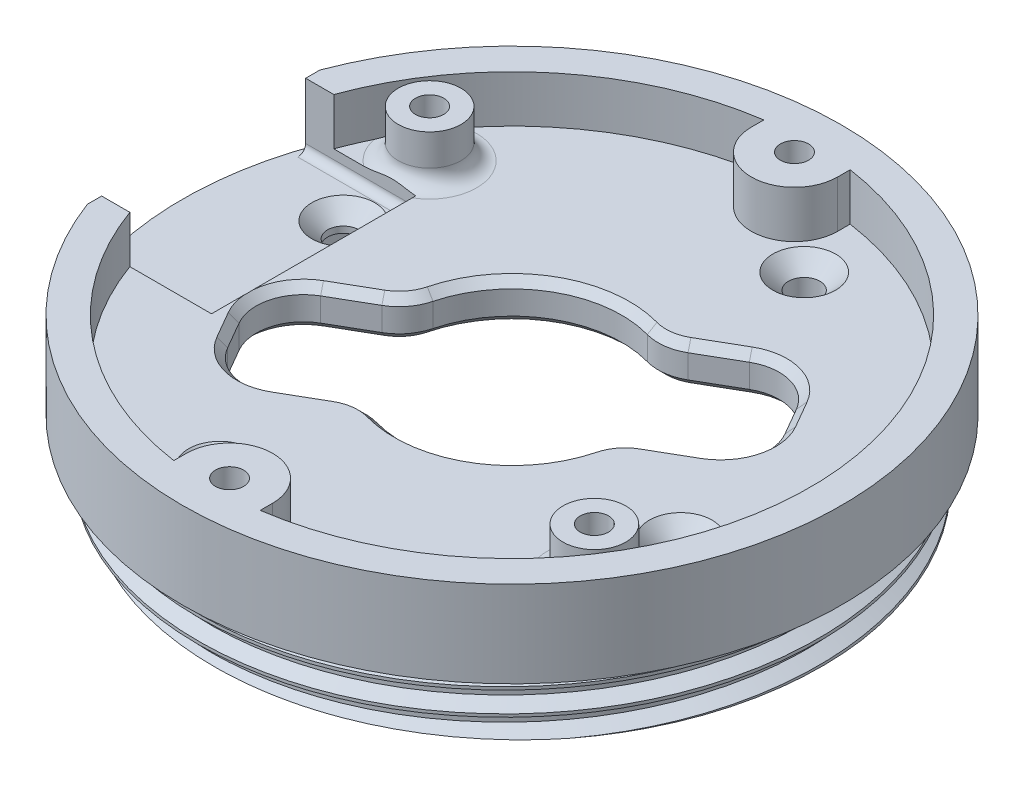
SolidWorks part; units mm, degrees
ref_plane "Front plane" through (0, 0, 0) normal (0, 0, 1) x (1, 0, 0)
ref_plane "Top plane" through (0, 0, 0) normal (0, 1, 0) x (1, 0, 0)
ref_plane "Right plane" through (0, 0, 0) normal (1, 0, 0) x (0, 0, -1)
ref_axis "Axis X" through (0, 0, 0) along (1, 0, 0)
ref_axis "Axis Y" through (0, 0, 0) along (0, 1, 0)
ref_axis "Axis Z" through (0, 0, 0) along (0, 0, 1)
sketch "Sketch1" plane through (0, 0, 0) normal (0, 1, 0) x (1, 0, 0)
  line L0 (0, 0) -> (0, 21) construction
  circle A0 centre (0, 0) radius 21
  circle A8 centre (0, 0) radius 7
  circle A9 centre (0, 0) radius 18 construction
  circle A10 centre (0, 18) radius 0.9
  circle A11 centre (0, -18) radius 0.9
  circle A12 centre (0, 0) radius 15.3 construction
  dimension "D1" = 42
  dimension "D9" = 14
  dimension "D10" = 36
  dimension "D11" = 1.8
  dimension "D12" = 1.8
  dimension "D5" = 30.6
extrude "Extrude1" add sketch "Sketch1" along normal blind 2.5
sketch "Sketch3" plane through (0, 2.5, 0) normal (0, 1, 0) x (1, 0, 0)
  line L0 (-2.75, 18) -> (-2.75, 18.7999)
  line L1 (2.75, 18) -> (2.75, 18.7999)
  line L2 (2.75, -18) -> (2.75, -18.7999)
  line L3 (-2.75, -18) -> (-2.75, -18.7999)
  line L5 (14.15, 8.9) -> (-14.15, 8.9) construction
  line L6 (14.15, 8.9) -> (14.15, -8.9) construction
  line L7 (14.15, -8.9) -> (-14.15, -8.9) construction
  line L8 (-14.15, 8.9) -> (-14.15, -8.9) construction
  line L9 (14.15, 8.9) -> (-14.15, -8.9) construction
  line L10 (14.15, -8.9) -> (-14.15, 8.9) construction
  arc A0 (-2.75, 18.7999) -> (-2.75, -18.7999) centre (0, 0) ccw
  circle A1 centre (0, 18) radius 0.9
  circle A2 centre (0, 0) radius 21 construction
  arc A3 (-2.75, 18) -> (2.75, 18) centre (0, 18) ccw
  arc A4 (2.75, -18) -> (-2.75, -18) centre (0, -18) ccw
  circle A5 centre (0, 0) radius 21
  arc A6 (-2.6256, -18.8177) -> (2.6256, -18.8177) centre (0, -18) ccw construction
  arc A7 (2.6256, 18.8177) -> (-2.6256, 18.8177) centre (0, 18) ccw construction
  arc A8 (2.6256, 18.8177) -> (-2.6256, 18.8177) centre (0, 0) ccw construction
  arc A9 (2.75, -18.7999) -> (2.75, 18.7999) centre (0, 0) ccw
  arc A10 (-2.6256, -18.8177) -> (2.6256, -18.8177) centre (0, 0) ccw construction
  circle A11 centre (0, -18) radius 0.9
  arc A12 (2.75, 18.7999) -> (2.6256, 18.8177) centre (0, 0) ccw construction
  arc A13 (2.75, 18) -> (2.6256, 18.8177) centre (0, 18) ccw construction
  arc A14 (-2.6256, 18.8177) -> (-2.75, 18.7999) centre (0, 0) ccw construction
  arc A15 (-2.6256, 18.8177) -> (-2.75, 18) centre (0, 18) ccw construction
  arc A16 (-2.75, -18) -> (-2.6256, -18.8177) centre (0, -18) ccw construction
  arc A17 (-2.75, -18.7999) -> (-2.6256, -18.8177) centre (0, 0) ccw construction
  arc A18 (2.6256, -18.8177) -> (2.75, -18) centre (0, -18) ccw construction
  arc A19 (2.6256, -18.8177) -> (2.75, -18.7999) centre (0, 0) ccw construction
  circle A20 centre (-14.15, 8.9) radius 2 construction
  circle A21 centre (14.15, -8.9) radius 2.2569 construction
  dimension "D2" = 5.5
  dimension "D3" = 5.5
  dimension "D5" = 1.8
  dimension "D6" = 1.8
  dimension "D9" = 4
  dimension "D10" = 4.5137
  dimension "D7" = 28.3
  dimension "D8" = 17.8
extrude "Extrude2" add sketch "Sketch3" along normal blind 3
sketch "Sketch7" plane through (0, 5.5, 0) normal (0, 1, 0) x (1, 0, 0)
  line L0 (0, 0) -> (-21, 0) construction
  line L1 (-17.4571, 7.5) -> (-17.4571, -7.5) construction
  line L2 (-15, 11.6619) -> (-15, -11.6619)
  circle A0 centre (0, 0) radius 21 construction
  arc A1 (-2.75, 18.7999) -> (-2.75, -18.7999) centre (0, 0) ccw construction
  arc A2 (-2.75, 18.7999) -> (-2.75, -18.7999) centre (0, 0) ccw construction
  arc A4 (-15, 11.6619) -> (-15, -11.6619) centre (0, 0) ccw
  arc A5 (-15, -11.6619) -> (-15, 11.6619) centre (0, 0) ccw construction
  dimension "D1" = 15
  dimension "D4" = 15
extrude "Extrude8" [suppressed] add sketch "Sketch7" against normal through all
sketch "Sketch4" plane through (0, 5.5, 0) normal (0, 1, 0) x (1, 0, 0)
  line L0 (0, 0) -> (-21, 0) construction
  line L1 (-21, 7.5) -> (-21, -7.5)
  line L3 (-12.65, 6.5) -> (-12.65, -6.5)
  line L6 (-21, 7.5) -> (-19.65, 7.5)
  line L8 (-19.65, 6.5) -> (-12.65, 6.5)
  line L9 (-19.65, -6.5) -> (-12.65, -6.5)
  line L10 (-21, -7.5) -> (-19.65, -7.5)
  line L11 (-19.65, 6.5) -> (-19.65, -6.5) construction
  line L12 (-19.65, 7.5) -> (-19.65, 6.5)
  line L13 (-19.65, -6.5) -> (-19.65, -7.5)
  circle A0 centre (0, 0) radius 21 construction
  point P11 (-21, 0)
  point P15 (-19.65, -7.5)
  point P19 (-12.65, 0)
  point P21 (-19.65, 7.5)
  dimension "D2" = 15
  dimension "D3" = 13
  dimension "D5" = 19.65
  dimension "D1" = 7
extrude "Extrude3" cut sketch "Sketch4" against normal blind 4.1
sketch "Sketch9" plane through (0, 0, 0) normal (0, -1, 0) x (1, 0, 0)
  circle A0 centre (0, 18) radius 1
  circle A1 centre (0, -18) radius 1
  dimension "D1" = 2
  dimension "D2" = 2
extrude "Extrude5" add sketch "Sketch9" against normal blind 1
sketch "Sketch8" plane through (0, 0, 0) normal (0, -1, 0) x (1, 0, 0)
  circle A0 centre (0, 0) radius 18
  circle A1 centre (0, 0) radius 18.95
  dimension "D1" = 36
  dimension "D2" = 0.95
extrude "Extrude6" add sketch "Sketch8" along normal blind 4
thread "Thread1" pitch 1.5 method extrude trim with start face yes trim with end face yes profile "Sketch11" start angle 0, offset 2, length 0, pitch 1.5, diameter 37.9
ref_plane "Plane1" through (18.95, -6, 0) normal (0, 0, 1) x (1, 0, 0)
sketch "Sketch11" plane through (18.95, -6, 0) normal (0, 0, 1) x (1, 0, 0)
  line L0 (0, 0) -> (0, 1.5) construction
  line L1 (0, 0) -> (0.8119, 0.4687)
  line L2 (0.8119, 0.4687) -> (0.8119, 0.6562)
  line L3 (0.8119, 0.6562) -> (0, 1.125)
  line L4 (0.8119, 0.5625) -> (0, 0.5625) construction
  line L11 (0, 0) -> (0, 1.125)
  point P2 (0, 0)
  dimension "Pitch" = 1.5
  dimension "Profile_Angle" = 60
  dimension "Profile_Land" = 0.1875
  dimension "Profile_Height" = 0.8119
fillet "Fillet3" [suppressed] radius 0.5
sketch "Sketch28" plane through (0, 1.4, 0) normal (0, 1, 0) x (1, 0, 0)
  line L0 (-17.8536, 6.5) -> (-17.8536, -6.5)
  arc A0 (-17.8536, 6.5) -> (-17.8536, -6.5) centre (0, 0) ccw
  arc A1 (-17.8536, -6.5) -> (-17.8536, 6.5) centre (0, 0) ccw construction
extrude "Extrude15" [suppressed] add sketch "Sketch28" against normal up to surface (0.6 mm away)
fillet "Fillet4" radius 0.5 2 edges at (-16.15, 1.4, 6.5) (-16.15, 1.4, -6.5)
sketch "Sketch22" plane through (0, 2.5, 0) normal (0, 1, 0) x (1, 0, 0)
  line L1 (14.15, 8.9) -> (-14.15, 8.9) construction
  line L2 (14.15, 8.9) -> (14.15, -8.9) construction
  line L3 (14.15, -8.9) -> (-14.15, -8.9) construction
  line L4 (-14.15, 8.9) -> (-14.15, -8.9) construction
  line L5 (14.15, 8.9) -> (-14.15, -8.9) construction
  line L6 (14.15, -8.9) -> (-14.15, 8.9) construction
  circle A1 centre (-14.15, 8.9) radius 2
  circle A2 centre (14.15, -8.9) radius 2
  point P0 (0, 0)
  dimension "D3" = 4
  dimension "D4" = 4
  dimension "D1" = 28.3
  dimension "D2" = 17.8
extrude "Extrude9" add sketch "Sketch22" along normal blind 3
sketch "Sketch23" plane through (0, 5.5, 0) normal (0, 1, 0) x (1, 0, 0)
  line L0 (0, 0) -> (3.9348, 14.6848) construction
  line L1 (0, 0) -> (0, 15.2028) construction
  line L6 (0, 0) -> (9.4981, -8.8746) construction
  circle A0 centre (14.15, -8.9) radius 0.9
  circle A1 centre (-14.15, 8.9) radius 0.9
  circle A2 centre (0, 0) radius 15.2028 construction
  circle A4 centre (3.9348, 14.6848) radius 1
  circle A5 centre (14.6848, -3.9348) radius 1
  circle A6 centre (-3.9348, -14.6848) radius 1
  circle A7 centre (-14.6848, 3.9348) radius 1
  point P21 (0, 0)
  dimension "D1" = 1.8
  dimension "D2" = 1.8
  dimension "D4" = 30.4056
  dimension "D5" = 2
  dimension "D3" = 15
extrude "Extrude10" cut sketch "Sketch23" against normal through all
sketch "Sketch24" plane through (0, 2.5, 0) normal (0, 1, 0) x (1, 0, 0)
  line L0 (3.9348, 14.6848) -> (0, 0) construction
  line L1 (8.6603, 5) -> (-8.6603, -5) construction
  line L2 (7.6603, 6.7321) -> (9.6603, 3.2679) construction
  line L3 (10.2583, 8.2321) -> (12.2583, 4.7679)
  line L4 (5.0622, 5.2321) -> (7.0622, 1.7679)
  line L5 (0, 0) -> (3.9532, -6.8471) construction
  line L6 (-9.6603, -3.2679) -> (-7.6603, -6.7321) construction
  line L7 (-12.2583, -4.7679) -> (-10.2583, -8.2321)
  line L8 (-7.0622, -1.7679) -> (-5.0622, -5.2321)
  arc A0 (10.2583, 8.2321) -> (5.0622, 5.2321) centre (7.6603, 6.7321) ccw
  arc A1 (7.0622, 1.7679) -> (12.2583, 4.7679) centre (9.6603, 3.2679) ccw
  arc A2 (-12.2583, -4.7679) -> (-7.0622, -1.7679) centre (-9.6603, -3.2679) cw
  arc A3 (-5.0622, -5.2321) -> (-10.2583, -8.2321) centre (-7.6603, -6.7321) cw
  circle A4 centre (3.9348, 14.6848) radius 1 construction
  point P6 (0, 0)
  point P9 (8.6603, 5)
  point P17 (-8.6603, -5)
  dimension "D3" = 4
  dimension "D1" = 10
  dimension "D2" = 6
  dimension "D4" = 45
extrude "Extrude11" [suppressed] cut sketch "Sketch24" against normal blind 40
chamfer "Chamfer1" [suppressed] distance 0.5 angle 45
sketch "Sketch25" plane through (0, 2.5, 0) normal (0, 1, 0) x (1, 0, 0)
  line L0 (9.2583, 9.9641) -> (-13.2583, -3.0359)
  line L1 (9.2583, 9.9641) -> (13.2583, 3.0359)
  line L2 (-13.2583, -3.0359) -> (-9.2583, -9.9641)
  line L3 (13.2583, 3.0359) -> (-9.2583, -9.9641)
  line L4 (9.2583, 9.9641) -> (-9.2583, -9.9641) construction
  line L5 (-13.2583, -3.0359) -> (13.2583, 3.0359) construction
  line L6 (0, 0) -> (3.9348, 14.6848) construction
  circle A0 centre (3.9348, 14.6848) radius 1 construction
  point P1 (0, 0)
  dimension "D1" = 26
  dimension "D2" = 45
  dimension "D3" = 8
extrude "Extrude12" cut sketch "Sketch25" against normal through all
fillet "Fillet5" radius 3 8 edges at (6.9749, 1.25, 0.5918) (2.9749, 1.25, -6.3364) (-6.9749, 1.25, -0.5918) (-2.9749, 1.25, 6.3364) (-9.2583, 1.25, 9.9641) (-13.2583, 0.7, 3.0359) (13.2583, 1.25, -3.0359) (9.2583, 1.25, -9.9641)
chamfer "Chamfer2" distance 0.5 angle 45 32 edges at (-9.4225, 0, 0.8213) (-12.058, 0, 3.3575) (-7.2955, 0, -0.6771) (-11.2583, 0, 6.5) (-3.5, 0, -6.0622) (-8.9367, 0, 8.7638) (3.0614, 0, -6.6566) (-5.4225, 0, 7.7495) (5.4225, 0, -7.7495) (-3.0614, 0, 6.6566) (8.9367, 0, -8.7638) (3.5, 0, 6.0622) (11.2583, 0, -6.5) (7.2955, 0, 0.6771) (12.058, 0, -3.3575) (9.4225, 0, -0.8213) (-3.0614, 2.5, 6.6566) (-5.4225, 2.5, 7.7495) (3.5, 2.5, 6.0622) (-8.9367, 2.5, 8.7638) (7.2955, 2.5, 0.6771) (-11.2583, 2.5, 6.5) (9.4225, 2.5, -0.8213) (-12.058, 2.5, 3.3575) (12.058, 2.5, -3.3575) (-9.4225, 2.5, 0.8213) (11.2583, 2.5, -6.5) (-7.2955, 2.5, -0.6771) (8.9367, 2.5, -8.7638) (-3.5, 2.5, -6.0622) (5.4225, 2.5, -7.7495) (3.0614, 2.5, -6.6566)
sketch "Sketch27" plane through (0, 2.5, 0) normal (0, 1, 0) x (1, 0, 0)
  line L0 (12.6848, -1.9348) -> (16.6848, -1.9348)
  line L1 (1.9348, 12.6848) -> (5.9348, 12.6848)
  line L2 (1.9348, 12.6848) -> (1.9348, 16.6848)
  line L3 (1.9348, 16.6848) -> (5.9348, 16.6848)
  line L4 (5.9348, 12.6848) -> (5.9348, 16.6848)
  line L5 (1.9348, 12.6848) -> (5.9348, 16.6848) construction
  line L6 (1.9348, 16.6848) -> (5.9348, 12.6848) construction
  line L7 (16.6848, -1.9348) -> (16.6848, -5.9348)
  line L8 (12.6848, -5.9348) -> (16.6848, -5.9348)
  line L9 (12.6848, -1.9348) -> (12.6848, -5.9348)
  line L10 (16.6848, -1.9348) -> (12.6848, -5.9348) construction
  line L11 (12.6848, -1.9348) -> (16.6848, -5.9348) construction
  line L12 (-1.9348, -12.6848) -> (-1.9348, -16.6848)
  line L13 (-1.9348, -16.6848) -> (-5.9348, -16.6848)
  line L14 (-5.9348, -12.6848) -> (-5.9348, -16.6848)
  line L15 (-1.9348, -12.6848) -> (-5.9348, -12.6848)
  line L16 (-1.9348, -16.6848) -> (-5.9348, -12.6848) construction
  line L17 (-1.9348, -12.6848) -> (-5.9348, -16.6848) construction
  line L18 (-12.6848, 1.9348) -> (-16.6848, 1.9348)
  line L19 (-16.6848, 1.9348) -> (-16.6848, 5.9348)
  line L20 (-12.6848, 5.9348) -> (-16.6848, 5.9348)
  line L21 (-12.6848, 1.9348) -> (-12.6848, 5.9348)
  line L22 (-16.6848, 1.9348) -> (-12.6848, 5.9348) construction
  line L23 (-12.6848, 1.9348) -> (-16.6848, 5.9348) construction
  circle A0 centre (3.9348, 14.6848) radius 2 construction
  circle A1 centre (3.9348, 14.6848) radius 1 construction
  circle A2 centre (14.6848, -3.9348) radius 2 construction
  circle A3 centre (-3.9348, -14.6848) radius 2 construction
  circle A4 centre (-14.6848, 3.9348) radius 2 construction
  circle A5 centre (-3.9348, -14.6848) radius 1 construction
  point P30 (0, 0)
  dimension "D1" = 1
  dimension "D2" = 4
extrude "Extrude14" [suppressed] cut sketch "Sketch27" along normal through all
chamfer "Chamfer3" distance 1 angle 45 3 edges at (-3.9348, 2.5, 15.6848) (14.6848, 2.5, 4.9348) (3.9348, 2.5, -13.6848)
fillet "Fillet6" radius 1 2 edges at (14.15, 2.5, 10.9) (-14.15, 2.5, -6.9)
fillet "Fillet7" [suppressed] radius 0.5
sketch "Эскиз2" plane through (0, 1.4, 0) normal (0, 1, 0) x (1, 0, 0)
  circle A0 centre (-14.6848, 3.9348) radius 2
  circle A2 centre (-14.6848, 3.9348) radius 1 construction
  dimension "D1" = 1
extrude "Вырез-Вытянуть1" [suppressed] cut sketch "Эскиз2" along normal up to surface (0.1 mm away)
chamfer "Фаска1" distance 1 angle 45 1 edges at (-14.6848, 1.4, -4.9348)
equation "\"motor_D\"= 34'Motor diameter"
equation "\"motor_H\"= 16'Motor heigh"
equation "\"motor_d1\"= 30.4056'Seating diameter of screws on the fixed part of the motor"
equation "\"motor_s1\"= 2'Screws diameter on the fixed part of motor"
equation "\"motor_d2\"= 0'Seating diameter of screws on the moving part of the motor (if this parameter is not determine, write 0)"
equation "\"motor_s2\"= 2.5'Screws diameter on the moving part of motor"
equation "\"motor_Dc\"= 5'Central hole diameter of motor"
equation "\"bearing_d1\"= 8'Bearing inner diameter"
equation "\"bearing_d2\"= 16'Bearing external diameter"
equation "\"bearing h\"= 5'Bearing heigh"
equation "\"pin_d\"= 2'Pin diameter"
equation "\"pin_h\"= 12'Pin heigh"
equation "\"D1@Sketch1\" = IIF ( \"motor_D\" < 34 , 41 , \"motor_D\" + 8 )"
equation "\"D9@Sketch1\"=\"motor_cmd\"+2"
equation "\"D10@Sketch1\"=\"D1@Sketch1\"-6"
equation "\"D4@Sketch3\"=\"D1@Sketch3\""
equation "\"D6@Sketch3\"=\"D5@Sketch3\""
equation "\"D5@Sketch1\"=\"motor_D\"*0.9"
equation "\"D1@Sketch8\" = IIF ( \"motor_D\" < 34 , 41 , \"motor_D\" + 8 ) - ( 42 - 36 )"
equation "\"D6@Thread1\"=\"motor_D\"+1.5+2"
equation "\"D4@Sketch7\"= IIF ( \"motor_D\" < 36 , 15 , 18 )"
equation "\"Extrude8\" = IIF ( \"motor_D\" < 36 , \"suppressed\" , \"unsuppressed\" )"
equation "\"motor_a2\"= 12'Seating parameter in rectangle of screws on the moving part of the motor"
equation "\"magnet_d1\"= 5'Magnet inner diameter"
equation "\"magnet_d2\"= 9.5'Magnet external diameter"
equation "\"magnet_h\"= 3'Magnet heigh"
equation "\"motor_b2\"= 22'Seating parameter in rectangle of screws on the moving part of the motor"
equation "\"motor_cmd\"= 12'Central magnet mount diameter"
equation "\"motor_cmh\"= 0.4'Central magnet mount heigh (if not write 0)"
equation "\"motor_whR\"= 10'Distance from center of motor to wires"
equation "\"D1@Extrude2\" = IIF ( \"motor_cmh\" = 0 , \"magnet_h\" + 1.5 + 3.6 - \"D1@Extrude1\" , \"motor_cmh\" + 1.5 + 3.6 - \"D1@Extrude1\" )"
equation "\"D1@Extrude1\"=2.5"
equation "\"D2@Sketch8\"=0.95"
equation "\"print_offset\"= 0.2'Offset for printing holes"
equation "\"D12@Sketch1\"=2-\"print_offset\""
equation "\"D11@Sketch1\"=\"D12@Sketch1\""
equation "\"D5@Sketch3\"=2-\"print_offset\""
equation "\"D5@Sketch4\"=19.65"
equation "\"Fillet3\"= IIF ( \"motor_D\" < 36 , \"suppressed\" , \"unsuppressed\" )"
equation "\"D3@Sketch22\"=\"D4@Sketch22\""
equation "\"D1@Extrude9\"= \"D1@Extrude2\""
equation "\"D1@Sketch23\"=2-\"print_offset\""
equation "\"D2@Sketch23\"=\"D1@Sketch23\""
equation "\"D4@Sketch23\"=\"motor_d1\""
equation "\"D5@Sketch23\"=\"motor_s1\""
equation "\"D1@Sketch24\"=\"motor_whR\""
equation "\"Extrude11\"= IIF ( ( \"motor_whR\" - 3 ) - \"motor_cmd\" < 1 , \"suppressed\" , \"unsuppressed\" )"
equation "\"Chamfer1\"= IIF ( ( \"motor_whR\" - 3 ) - \"motor_cmd\" < 1 , \"suppressed\" , \"unsuppressed\" )"
equation "\"D1@Sketch25\"=\"motor_cmd\"+8+6"
equation "\"Extrude12\"= IIF ( ( \"motor_whR\" - 3 ) - \"motor_cmd\" > 1 , \"suppressed\" , \"unsuppressed\" )"
equation "\"Fillet5\"= IIF ( ( \"motor_whR\" - 3 ) - \"motor_cmd\" > 1 , \"suppressed\" , \"unsuppressed\" )"
equation "\"Chamfer2\"= IIF ( ( \"motor_whR\" - 3 ) - \"motor_cmd\" > 1 , \"suppressed\" , \"unsuppressed\" )"
equation "\"Fillet7\"= IIF ( ( \"motor_d1\" + \"motor_s1\" + 2 ) / 2 > 18 , \"unsuppressed\" , \"suppressed\" )"
equation "\"Extrude14\"= IIF ( ( \"motor_d1\" + \"motor_s1\" + 2 ) / 2 > 18 , \"unsuppressed\" , \"suppressed\" )"
equation "\"ft_sensor_d1\"= 9.8"
equation "\"ft_sensor_d2\"= 24.9"
equation "\"ft_sensor_d3\"= 22.6'Inner diameter of "
equation "\"ft_sensor_h\"= 7.1"
equation "\"ft_sensor_whD\" = 5"
equation "\"Extrude15\"= IIF ( \"motor_cmh\" = 0 , \"unsuppressed\" , \"suppressed\" )"
equation "\"Вырез-Вытянуть1\"= IIF ( \"motor_d1\" + \"motor_s1\" > 13.8 * 2 , \"suppressed\" , \"unsuppressed\" )"
equation "\"Extrude3\"= IIF ( \"motor_D\" < 34 , \"unsuppressed\" , \"suppressed\" )"
